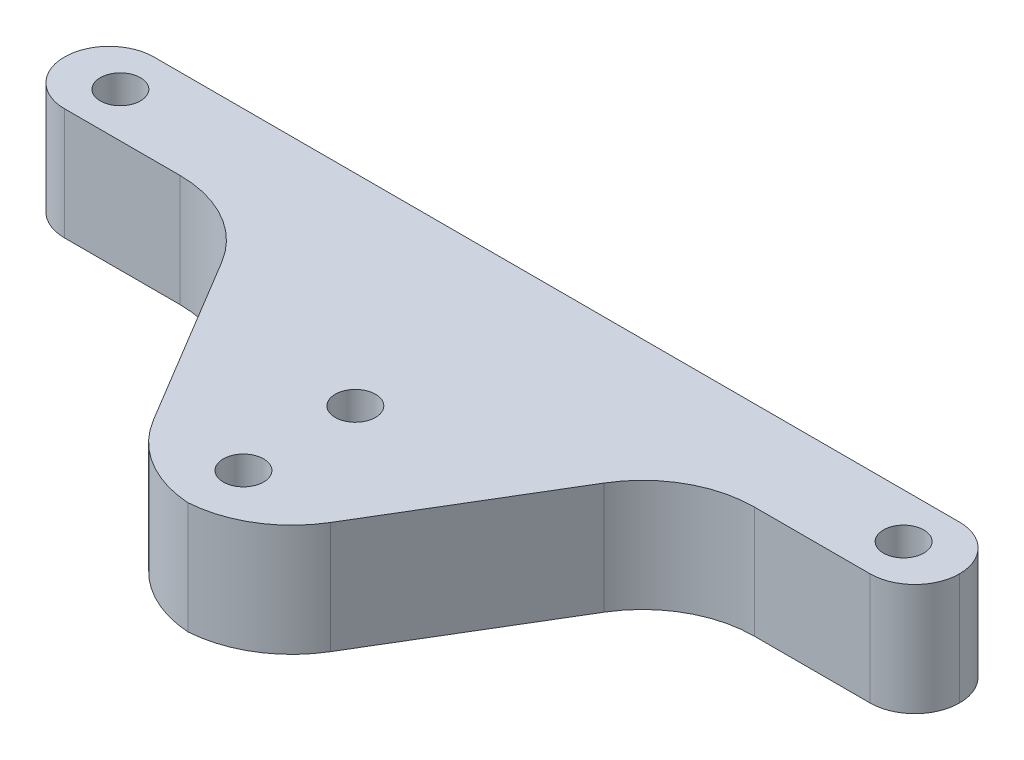
SolidWorks part; units mm, degrees
ref_plane "Front Plane" through (0, 0, 0) normal (0, 0, 1) x (1, 0, 0)
ref_plane "Top Plane" through (0, 0, 0) normal (0, 1, 0) x (1, 0, 0)
ref_plane "Right Plane" through (0, 0, 0) normal (1, 0, 0) x (0, 0, -1)
sketch "Sketch2" plane through (0, 0, 0) normal (0, 1, 0) x (1, 0, 0)
  line L6 (-6.35, 0) -> (6.35, 0)
  line L8 (25.4, 31.75) -> (50.8, 31.75)
  line L9 (50.8, 31.75) -> (50.8, 41.91)
  line L10 (50.8, 41.91) -> (-50.8, 41.91)
  line L11 (0, 41.91) -> (0, 0) construction
  line L14 (-50.8, 31.75) -> (-50.8, 41.91)
  line L15 (6.35, 0) -> (25.4, 31.75)
  line L17 (-25.4, 31.75) -> (-50.8, 31.75)
  line L18 (-6.35, 0) -> (-25.4, 31.75)
  circle A0 centre (0, 19.05) radius 2.286
  circle A1 centre (0, 6.35) radius 2.286
  circle A2 centre (44.45, 36.83) radius 2.286
  circle A3 centre (-44.45, 36.83) radius 2.286
  point P2 (25.9784, 31.9961)
  dimension "D1" = 4.572
  dimension "D2" = 5.08
  dimension "D3" = 6.35
  dimension "D4" = 10.16
  dimension "D5" = 6.35
  dimension "D6" = 12.7
  dimension "D7" = 6.35
  dimension "D8" = 12.7
  dimension "D9" = 50.8
  dimension "D10" = 25.4
extrude "Boss-Extrude2" add sketch "Sketch2" along normal blind 12.7
fillet "Fillet1" radius 5.08 4 edges at (50.8, 6.35, -41.91) (50.8, 6.35, -31.75) (-50.8, 6.35, -41.91) (-50.8, 6.35, -31.75)
fillet "Fillet2" radius 12.7 4 edges at (-25.4, 6.35, -31.75) (-6.35, 6.35, 0) (6.35, 6.35, 0) (25.4, 6.35, -31.75)
